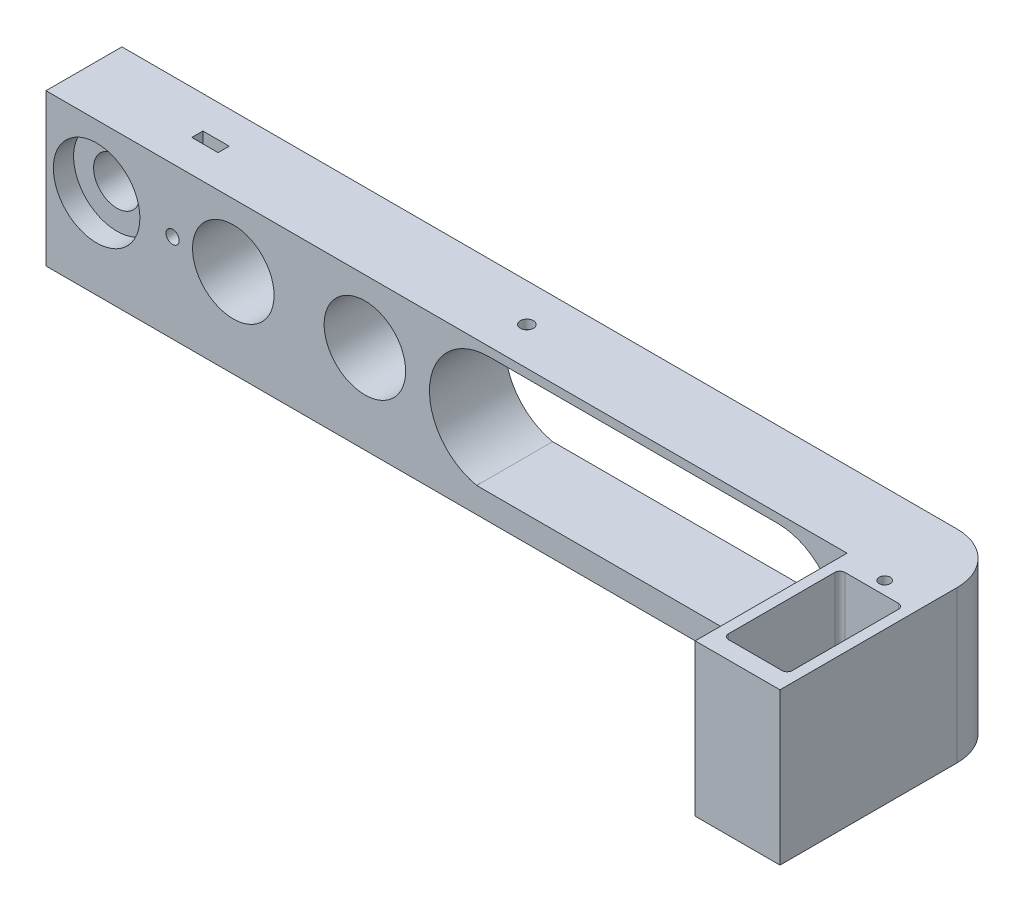
SolidWorks part; units mm, degrees
ref_plane "Front Plane" through (0, 0, 0) normal (0, 0, 1) x (1, 0, 0)
ref_plane "Top Plane" through (0, 0, 0) normal (0, 1, 0) x (1, 0, 0)
ref_plane "Right Plane" through (0, 0, 0) normal (1, 0, 0) x (0, 0, -1)
sketch "Sketch1" plane through (0, 0, 0) normal (0, 1, 0) x (1, 0, 0)
  line L1 (-87.5, -7.5) -> (87.5, -7.5)
  line L2 (-87.5, -7.5) -> (-87.5, 7.5)
  line L3 (-87.5, 7.5) -> (87.5, 7.5)
  line L4 (87.5, -7.5) -> (87.5, 7.5)
  line L5 (-87.5, -7.5) -> (87.5, 7.5) construction
  line L6 (-87.5, 7.5) -> (87.5, -7.5) construction
  point P0 (0, 0)
  dimension "D1" = 175
  dimension "D2" = 15
extrude "Boss-Extrude1" add sketch "Sketch1" along normal blind 25
sketch "Sketch3" plane through (0, 0, 7.5) normal (0, 0, 1) x (1, 0, 0)
  line L0 (-87.5, 25) -> (-87.5, 0) construction
  line L1 (-50.5, 12.5) -> (-24.5, 12.5) construction
  circle A1 centre (-77.5, 12.5) radius 8.55
  circle A2 centre (-77.5, 12.5) radius 4.6
  circle A3 centre (-50.5, 12.5) radius 8.05
  circle A4 centre (-24.5, 12.5) radius 8.05
  circle A5 centre (-62.5, 12.5) radius 1.3
  point P9 (-12.9257, 12.5)
  point P10 (-37.5, 12.5)
  point P12 (0, 0)
  point P16 (-87.5, 12.5)
  dimension "D1" = 17.1
  dimension "D2" = 9.2
  dimension "D3" = 16.1
  dimension "D4" = 9.9
  dimension "D5" = 2.6
  dimension "D6" = 10
  dimension "D7" = 15
  dimension "D8" = 25
extrude "Cut-Extrude1" cut sketch "Sketch3" against normal up to next contours A2 | A5 | A3 | A4 region at (-77.5, 12.5, 7.5) region at (-50.5, 12.5, 7.5) region at (-24.5, 12.5, 7.5) region at (-62.5, 12.5, 7.5)
extrude "Cut-Extrude2" cut sketch "Sketch3<3>" against normal blind 4 contours A1 A2 region at (-85.8082, 12.5, 7.5)
sketch "Sketch3<3>" plane through (0, 0, 7.5) normal (0, 0, 1) x (1, 0, 0) same geometry as "Sketch3"
sketch "Sketch4" plane through (0, 0, 0) normal (0, 0, 1) x (1, 0, 0)
  line L0 (-65.1, 14.0011) -> (-65.1, 25)
  line L1 (-62.5, 15.5022) -> (-65.1, 14.0011)
  line L2 (-65.1, 14.0011) -> (-65.1, 10.9989)
  line L3 (-65.1, 10.9989) -> (-62.5, 9.4978)
  line L4 (-62.5, 9.4978) -> (-59.9, 10.9989)
  line L5 (-59.9, 10.9989) -> (-59.9, 14.0011)
  line L6 (-59.9, 14.0011) -> (-62.5, 15.5022)
  line L7 (-87.5, 25) -> (87.5, 25) construction
  line L8 (-65.1, 25) -> (-59.9, 25)
  line L9 (-59.9, 25) -> (-59.9, 14.0011)
  circle A0 centre (-62.5, 12.5) radius 2.6 construction
  point P1 (-10.2748, 25)
  point P14 (0, 0)
  dimension "D1" = 5.2
extrude "Cut-Extrude3" cut sketch "Sketch4" against normal mid plane 2.2 contours L5 L6 L1 L2 L3 L4 | L9 L8 L0 L1 L6 region at (-62.5, 19.8667, 0) region at (-62.5, 12.5, 0)
sketch "Sketch5" plane through (0, 25, 0) normal (0, 1, 0) x (1, 0, 0)
  circle A0 centre (0, 0) radius 1.3
  dimension "D1" = 2.6
extrude "Cut-Extrude4" cut sketch "Sketch5" against normal up to next
sketch "Sketch6" plane through (0, 0, 7.5) normal (0, 0, 1) x (1, 0, 0)
  line L0 (0, 11.5) -> (57, 11.5) construction
  line L1 (0, 23) -> (57, 23)
  line L2 (0, 0) -> (57, 0)
  line L4 (28.5, 11.5) -> (28.5, -7.044) construction
  line L5 (0, 23.25) -> (57, 23.25)
  line L6 (0, -0.25) -> (57, -0.25)
  line L7 (0, 26.25) -> (57, 26.25)
  line L8 (0, -3.25) -> (57, -3.25)
  line L9 (-9.2365, 0) -> (66.2365, 0)
  line L10 (-87.5, 0) -> (87.5, 0) construction
  arc A0 (0, 23) -> (0, 0) centre (0, 11.5) ccw
  arc A1 (57, 0) -> (57, 23) centre (57, 11.5) ccw
  arc A2 (57, -0.25) -> (57, 23.25) centre (57, 11.5) ccw
  arc A3 (0, 23.25) -> (0, -0.25) centre (0, 11.5) ccw
  arc A4 (57, -3.25) -> (57, 26.25) centre (57, 11.5) ccw
  arc A5 (0, 26.25) -> (0, -3.25) centre (0, 11.5) ccw
  point P2 (28.5, 11.5)
  point P3 (46.0233, 11.4584)
  point P11 (46.4575, 6.2039)
  point P28 (21.2868, 26.25)
  point P29 (22.1323, 11.5)
  point P30 (0, 0)
  point P31 (0, 0)
  point P32 (0, 0)
  point P33 (64.5891, 11.5)
  point P34 (0, 0)
  line M26 (-87.5, 0) -> (87.5, 0)
  dimension "D2" = 80
  dimension "D1" = 23
  dimension "D3" = 0.25
  dimension "D4" = 3
extrude "Cut-Extrude6" cut sketch "Sketch6" against normal up to next contours A1 L1 A0 M26 | L5 A3 L9 A0 L1 A1 A2 M26 region at (-11.5838, 11.5, 7.5) region at (28.5, 11.5, 7.5)
sketch "Sketch8" plane through (0, 0, 0) normal (0, -1, 0) x (1, 0, 0)
  line L1 (-87.5, 7.5) -> (87.5, 7.5)
  line L2 (-87.5, 7.5) -> (-87.5, -7.5)
  line L3 (-87.5, -7.5) -> (87.5, -7.5)
  line L4 (87.5, 7.5) -> (87.5, -7.5)
extrude "Boss-Extrude2" add sketch "Sketch8" along normal blind 5
sketch "Sketch9" plane through (0, 0, 7.5) normal (0, 0, 1) x (1, 0, 0)
  line L0 (87.5, -5) -> (-87.5, -5) construction
  line L1 (87.5, 25) -> (70.75, 25)
  line L2 (87.5, 25) -> (87.5, -5)
  line L3 (87.5, -5) -> (70.75, -5)
  line L4 (70.75, 25) -> (70.75, -5)
  arc A1 (59.4109, 0) -> (57, 23.25) centre (57, 11.5) ccw construction
  dimension "D1" = 2
extrude "Boss-Extrude3" add sketch "Sketch9" along normal blind 30
sketch "Sketch10" plane through (0, 25, 0) normal (0, 1, 0) x (1, 0, 0)
  line L0 (87.5, -37.5) -> (70.75, -37.5) construction
  line L1 (73.825, -34) -> (84.425, -34)
  line L2 (72.825, -33) -> (72.825, -12)
  line L3 (73.825, -11) -> (84.425, -11)
  line L4 (85.425, -33) -> (85.425, -12)
  line L5 (70.75, -37.5) -> (70.75, -7.5) construction
  arc A0 (73.825, -34) -> (72.825, -33) centre (73.825, -33) cw
  arc A1 (84.425, -34) -> (85.425, -33) centre (84.425, -33) ccw
  arc A2 (84.425, -11) -> (85.425, -12) centre (84.425, -12) cw
  arc A3 (72.825, -12) -> (73.825, -11) centre (73.825, -12) cw
  circle A4 centre (79.125, -8.45) radius 1.1
  point P6 (79.125, -37.5)
  point P7 (79.125, -34)
  point P9 (79.125, -11)
  point P12 (70.75, -22.5)
  point P13 (72.825, -22.5)
  point P20 (85.425, -11)
  point P23 (72.825, -11)
  dimension "D3" = 1
  dimension "D4" = 1.45
  dimension "D5" = 2.2
  dimension "D1" = 23
  dimension "D2" = 12.6
extrude "Cut-Extrude7" cut sketch "Sketch10" against normal blind 30
fillet "Fillet1" radius 10 1 edges at (87.5, 10, -7.5)
